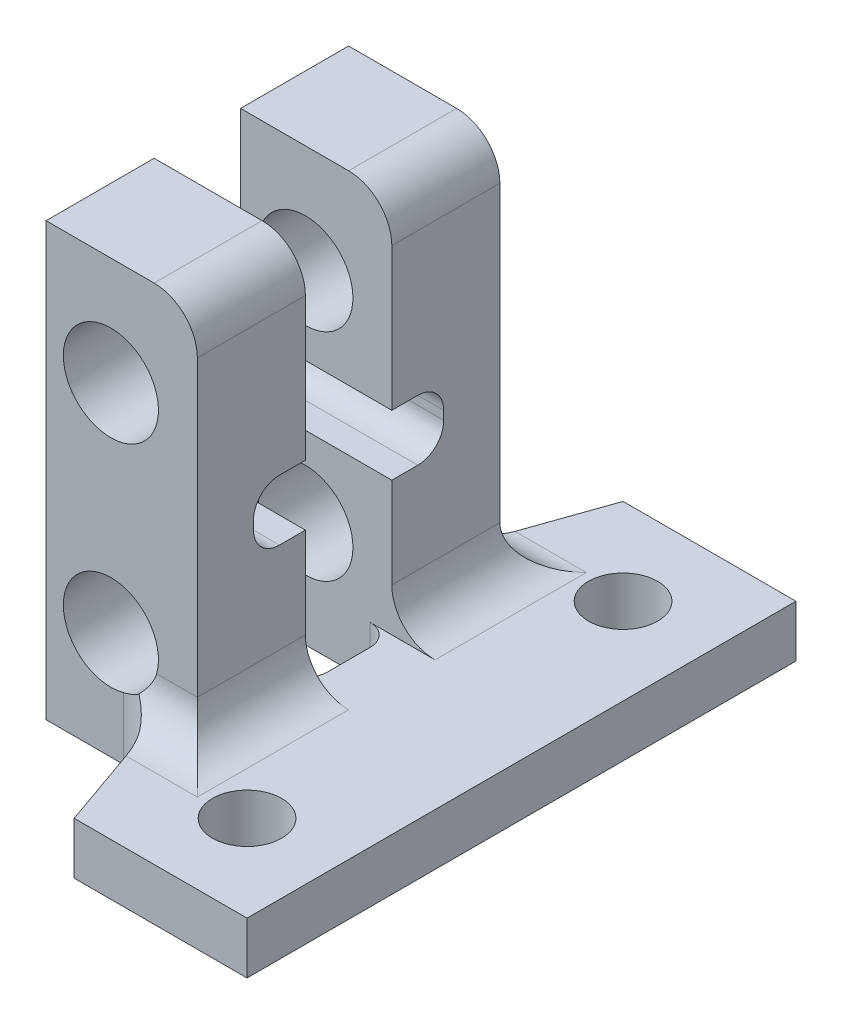
SolidWorks part; units mm, degrees
ref_plane "Alzado" through (0, 0, 0) normal (0, 0, 1) x (1, 0, 0)
ref_plane "Planta" through (0, 0, 0) normal (0, 1, 0) x (1, 0, 0)
ref_plane "Vista lateral" through (0, 0, 0) normal (1, 0, 0) x (0, 0, -1)
sketch "Croquis1" plane through (0, 0, 0) normal (1, 0, 0) x (0, 0, -1)
  line L0 (0, 0) -> (0, 10) construction
  line L1 (-12.7, 0) -> (12.7, 0)
  line L2 (12.7, 0) -> (12.7, 2.4)
  line L3 (12.7, 2.4) -> (7, 2.4)
  line L4 (7, 2.4) -> (7, 20)
  line L5 (7, 20) -> (2, 20)
  line L6 (2, 20) -> (2, 2.4)
  line L7 (2, 2.4) -> (-2, 2.4)
  line L8 (0, 10) -> (2, 10) construction
  line L9 (2, 10) -> (4.4, 10) construction
  line L10 (4.4, 11.4) -> (4.4, 8.6)
  line L11 (4.4, 8.6) -> (2, 8.6)
  line L12 (4.4, 11.4) -> (2, 11.4)
  line L13 (-4.4, 11.4) -> (-2, 11.4)
  line L14 (-4.4, 11.4) -> (-4.4, 8.6)
  line L15 (-4.4, 8.6) -> (-2, 8.6)
  line L16 (-7, 20) -> (-2, 20)
  line L17 (-12.7, 0) -> (-12.7, 2.4)
  line L18 (-2, 20) -> (-2, 2.4)
  line L19 (-7, 2.4) -> (-7, 20)
  line L20 (-12.7, 2.4) -> (-7, 2.4)
  line L21 (-7, 2.4) -> (-2, 2.4)
  line L22 (2, 2.4) -> (7, 2.4)
  point P15 (4.4, 10)
  point P26 (0, 2.4)
  dimension "D1" = 2.4
  dimension "D2" = 20
  dimension "D3" = 12.7
  dimension "D4" = 2
  dimension "D5" = 5
  dimension "D6" = 10
  dimension "D7" = 2.8
  dimension "D8" = 2.4
extrude "Saliente-Extruir1" add sketch "Croquis1" against normal blind 5 contours L19 L21 L18 L16 | L6 L22 L4 L5 L12 L10 L11 | L22 L7 L21 L20 L17 L1 L2 L3 region at (0, 1.2, 0) region at (0, 11.2992, 4.6075) region at (0, 11.2992, -4.6075)
extrude "Saliente-Extruir2" add sketch "Croquis1<3>" along normal blind 10 contours L22 L7 L21 L20 L17 L1 L2 L3 region at (0, 1.2, 0)
sketch "Croquis1<3>" plane through (0, 0, 0) normal (1, 0, 0) x (0, 0, -1) same geometry as "Croquis1"
extrude "Saliente-Extruir3" add sketch "Croquis1<4>" along normal blind 2 contours L19 L21 L18 L16 | L6 L22 L4 L5 L12 L10 L11 region at (0, 11.2992, 4.6075) region at (0, 11.2992, -4.6075)
sketch "Croquis1<4>" plane through (0, 0, 0) normal (1, 0, 0) x (0, 0, -1) same geometry as "Croquis1"
sketch "Croquis2" plane through (0, 0, 0) normal (0, 0, 1) x (1, 0, 0)
  line L0 (0, 0) -> (-2, 0) construction
  line L1 (-5, 0) -> (10, 0) construction
  line L2 (-2, 0) -> (-2, 20) construction
  line L3 (-5, 20) -> (2, 20) construction
  line L4 (-2, 5) -> (-2, 15) construction
  circle A0 centre (-2, 15) radius 2.2
  circle A1 centre (-2, 5) radius 2.2
  point P11 (-2, 10)
  dimension "D3" = 4.4
  dimension "D1" = 2
  dimension "D2" = 10
extrude "Cortar-Extruir1" cut sketch "Croquis2" against normal up to surface (7 mm away) from surface up to face at (-1.5, 11.2, -7) starting at face at (-1.5, 11.2, 7)
sketch "Croquis3" plane through (0, 0, 0) normal (0, 1, 0) x (1, 0, 0)
  line L0 (2, 0) -> (10, 0) construction
  line L2 (6, 8.7) -> (6, -8.7) construction
  line L3 (0, 7) -> (0, -7)
  line L4 (-5, 12.7) -> (2, 12.7)
  line L5 (-5, 12.7) -> (-5, 7)
  line L6 (-5, 7) -> (2, 7)
  line L7 (2, 12.7) -> (2, 7)
  line L8 (2, -7) -> (-5, -7)
  line L9 (2, -7) -> (2, -12.7)
  line L10 (2, -12.7) -> (-5, -12.7)
  line L11 (-5, -7) -> (-5, -12.7)
  line L12 (0, -7) -> (2, -12.7)
  line L13 (0, 7) -> (2, 12.7)
  line L14 (10, -12.7) -> (10, 12.7) construction
  line L15 (2, 0) -> (2, 2) construction
  line L16 (-5, 12.7) -> (10, 12.7) construction
  line L18 (-5, 2) -> (2, 2)
  line L19 (-5, 2) -> (-5, -2)
  line L20 (-5, -2) -> (2, -2)
  line L21 (2, 2) -> (2, -2)
  circle A0 centre (6, 8.7) radius 1.6
  circle A1 centre (6, -8.7) radius 1.6
  point P8 (6, 0)
  point P23 (0, 0)
  point P26 (6, 0)
  dimension "D2" = 3.2
  dimension "D3" = 3.2
  dimension "D1" = 4
extrude "Cortar-Extruir2" cut sketch "Croquis3" along normal up to surface (2.4 mm away) contours L6 L13 L4 L5 | L12 L8 L11 L10 | A1 | A0 | L19 L20 L3 L18 | L21 L18 L3 L20 region at (-1.9722, 0, 10.0083) region at (1, 0, 0) region at (-2.5, 0, 0) region at (-1.9722, 0, -10.0083) region at (6, 0, -8.7) region at (6, 0, 8.7) up to face at (-0.1667, 2.4, 0)
fillet "Redondeo1" radius 2 2 edges at (2, 20, -4.5) (2, 20, 4.5)
fillet "Redondeo2" radius 2 6 edges at (0, 1.2, -7) (1, 2.4, -7) (2, 2.4, -4.5) (2, 2.4, 4.5) (1, 2.4, 7) (0, 1.2, 7)
fillet "Redondeo3" radius 1 2 edges at (2, 1.2, 2) (2, 1.2, -2)
fillet "Redondeo4" radius 1.2 4 edges at (-1.5, 11.4, -4.4) (-1.5, 8.6, -4.4) (-1.5, 11.4, 4.4) (-1.5, 8.6, 4.4)
